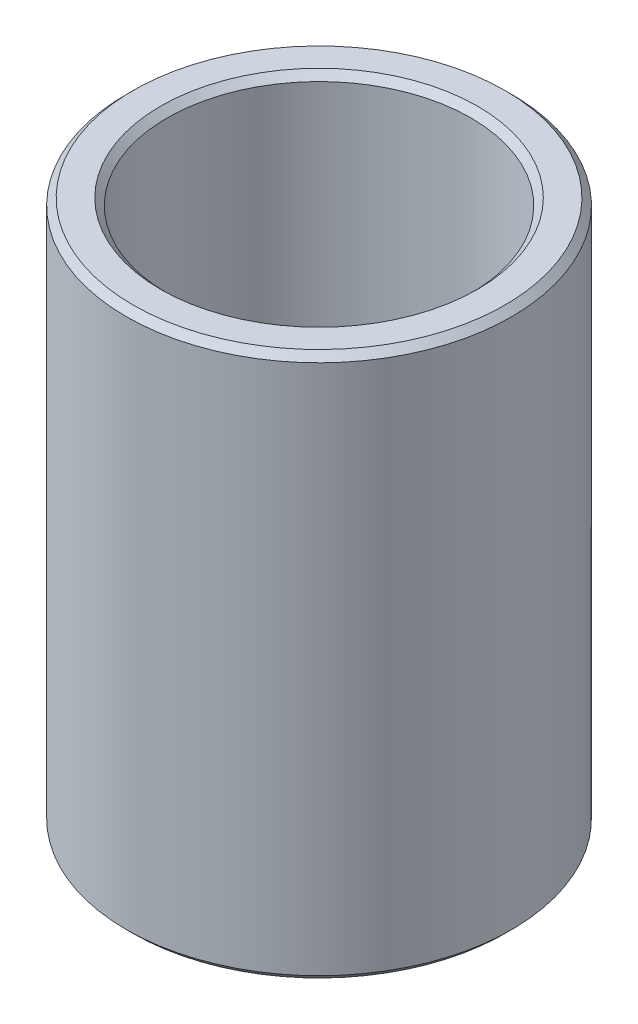
SolidWorks part; units mm, degrees
ref_plane "Front Plane" through (0, 0, 0) normal (0, 0, 1) x (1, 0, 0)
ref_plane "Top Plane" through (0, 0, 0) normal (0, 1, 0) x (1, 0, 0)
ref_plane "Right Plane" through (0, 0, 0) normal (1, 0, 0) x (0, 0, -1)
sketch "Sketch1" plane through (0, 0, 0) normal (0, 1, 0) x (1, 0, 0)
  circle A0 centre (0, 0) radius 20
  dimension "SLEEVE_OD" = 40
extrude "Boss-Extrude1" add sketch "Sketch1" along normal blind 56.5095
sketch "Sketch2" plane through (0, 0, 0) normal (0, 1, 0) x (1, 0, 0)
  circle A0 centre (0, 0) radius 15.7655
  dimension "BORE_D" = 31.531
extrude "Cut-Extrude1" cut sketch "Sketch2" along normal through all
chamfer "Chamfer1" distance 0.6997 angle 45 4 edges at (0, 56.5095, 15.7655) (0, 0, 15.7655) (0, 0, 20) (0, 56.5095, 20)
